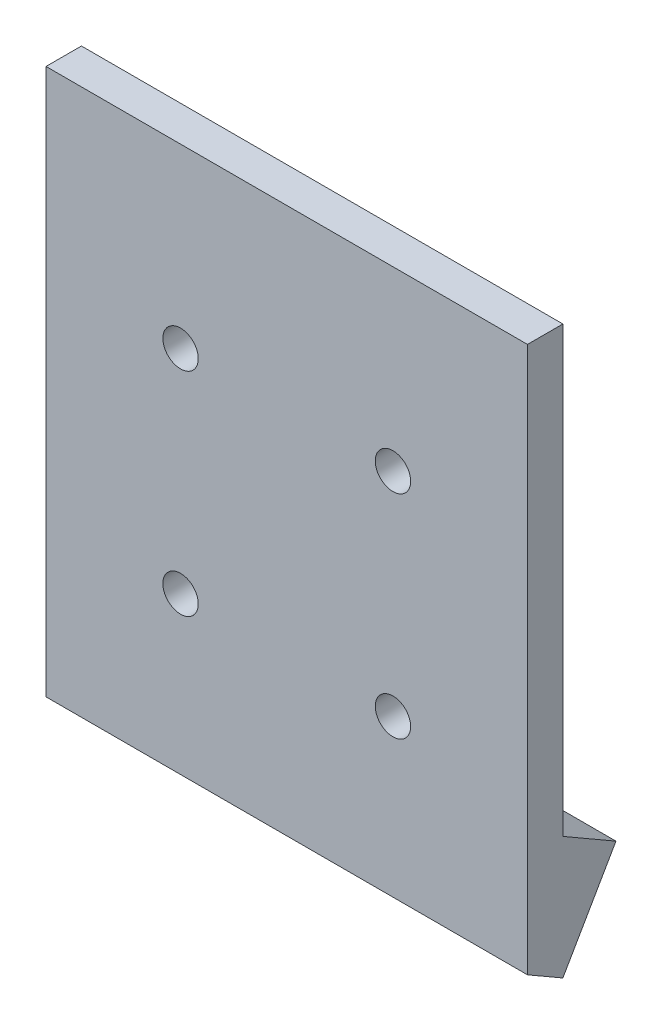
SolidWorks part; units mm, degrees
material "1060 Alloy"
ref_plane "Front Plane" through (0, 0, 0) normal (0, 0, 1) x (1, 0, 0)
ref_plane "Top Plane" through (0, 0, 0) normal (0, 1, 0) x (1, 0, 0)
ref_plane "Right Plane" through (0, 0, 0) normal (1, 0, 0) x (0, 0, -1)
sketch "Sketch1" plane through (0, 0, 0) normal (0, 0, 1) x (1, 0, 0)
  line L0 (-19.05, 19.05) -> (19.05, 19.05) construction
  line L1 (-43.18, -50.8) -> (43.18, -50.8)
  line L2 (-43.18, -50.8) -> (-43.18, 50.8)
  line L3 (-43.18, 50.8) -> (43.18, 50.8)
  line L4 (43.18, -50.8) -> (43.18, 50.8)
  line L5 (-43.18, -50.8) -> (43.18, 50.8) construction
  line L6 (-43.18, 50.8) -> (43.18, -50.8) construction
  line L7 (19.05, 19.05) -> (19.05, -19.05) construction
  line L8 (19.05, -19.05) -> (-19.05, -19.05) construction
  line L9 (-19.05, -19.05) -> (-19.05, 19.05) construction
  line L10 (-19.05, 19.05) -> (19.05, -19.05) construction
  line L11 (19.05, 19.05) -> (-19.05, -19.05) construction
  circle A0 centre (-19.05, 19.05) radius 3.175
  circle A1 centre (19.05, 19.05) radius 3.175
  circle A2 centre (-19.05, -19.05) radius 3.175
  circle A3 centre (19.05, -19.05) radius 3.175
  point P0 (0, 0)
  point P14 (0, 0)
  dimension "D1" = 6.35
  dimension "D2" = 38.1
  dimension "D3" = 38.1
  dimension "D4" = 86.36
  dimension "D5" = 101.6
extrude "Boss-Extrude1" add sketch "Sketch1" along normal blind 6.35
sketch "Sketch2" plane through (43.18, 0, 0) normal (1, 0, 0) x (0, 0, -1)
  line L0 (0, -50.8) -> (-6.35, -47.1338)
  line L1 (-6.35, -50.8) -> (-6.35, 50.8) construction
  line L2 (-6.35, -47.1338) -> (-6.35, -50.8)
  line L3 (-6.35, -50.8) -> (0, -50.8)
  dimension "D1" = 30
extrude "Cut-Extrude1" cut sketch "Sketch2" against normal through all
sketch "Sketch3" plane through (43.18, 0, 0) normal (1, 0, 0) x (0, 0, -1)
  line L0 (0, -50.8) -> (9.525, -34.3022)
  line L1 (9.525, -34.3022) -> (0, -28.803)
  line L2 (0, -50.8) -> (0, 50.8) construction
  line L3 (0, -28.803) -> (0, -50.8)
  line L4 (0, -50.8) -> (-6.35, -47.1338) construction
  dimension "D1" = 30
  dimension "D2" = 19.05
extrude "Boss-Extrude2" add sketch "Sketch3" against normal through all
sketch "Sketch4" plane through (0, -38.1, 21.997) normal (0, -0.866, 0.5) x (-1, 0, 0)
  line L0 (-43.18, 21.7338) -> (43.18, 21.7338) construction
  line L1 (-43.18, 25.4) -> (-43.18, 18.0677) construction
  line L2 (43.18, 25.4) -> (43.18, 18.0677) construction
  circle A0 centre (31.75, 21.7338) radius 2.1828
  circle A1 centre (-31.75, 21.7338) radius 2.1828
  dimension "D1" = 63.5
  dimension "D3" = 4.3656
  dimension "D2" = 11.43
extrude "Cut-Extrude2" cut sketch "Sketch4" against normal through all
